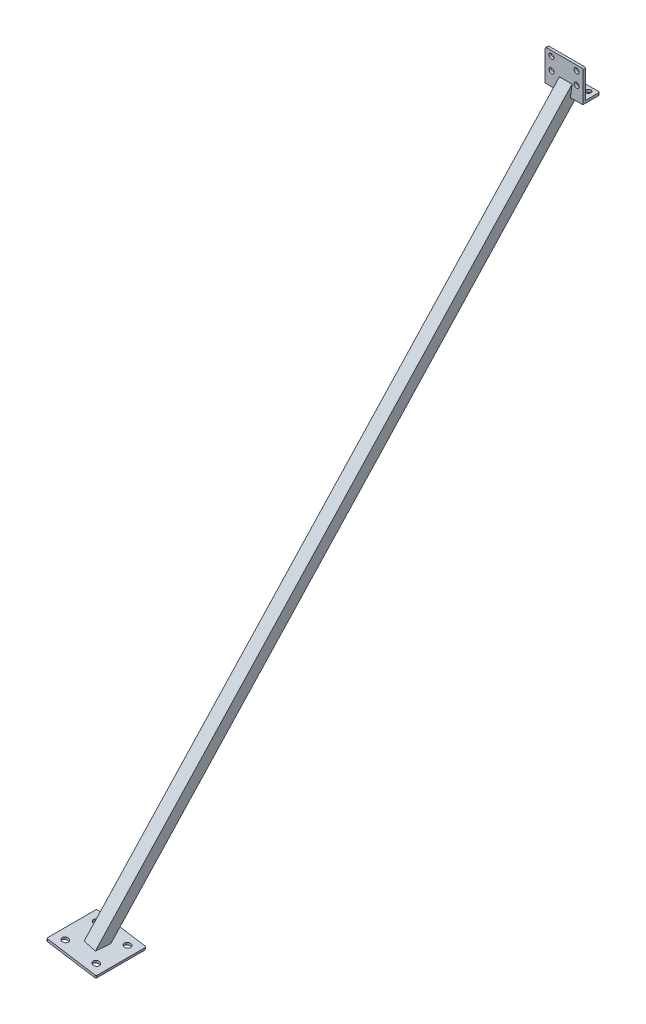
SolidWorks part; units mm, degrees
ref_plane "Front Plane" through (0, 0, 0) normal (0, 0, 1) x (1, 0, 0)
ref_plane "Top Plane" through (0, 0, 0) normal (0, 1, 0) x (1, 0, 0)
ref_plane "Right Plane" through (0, 0, 0) normal (1, 0, 0) x (0, 0, -1)
sketch "Sketch1" plane through (0, 0, 0) normal (1, 0, 0) x (0, 0, -1)
  line L0 (0, 0) -> (0, 50)
  line L1 (0, 50) -> (4, 50)
  line L2 (4, 50) -> (4, 4)
  line L3 (4, 4) -> (27, 4)
  line L4 (27, 4) -> (27, 0)
  line L5 (27, 0) -> (0, 0)
  dimension "D1" = 4
  dimension "D2" = 4
  dimension "D3" = 50
  dimension "D4" = 27
extrude "Boss-Extrude1" add sketch "Sketch1" along normal blind 60
ref_plane "Plane1" through (0, 0, 0) normal (0, -0.866, 0.5) x (-1, 0, 0)
sketch "Sketch2" plane through (0, 0, 0) normal (0, -0.866, 0.5) x (-1, 0, 0)
  line L0 (-30, 0) -> (-30, 23.3827)
  line L1 (-60, 0) -> (0, 0) construction
  line L2 (-60, 23.3827) -> (0, 23.3827) construction
ref_plane "Plane2" through (0.7342, 4.0142, -2.3176) normal (-0.1564, -0.8554, 0.4938) x (0, -0.5, -0.866)
sketch "Sketch3" plane through (0.7342, 4.0142, -2.3176) normal (-0.1564, -0.8554, 0.4938) x (0, -0.5, -0.866)
  line L0 (-9, 38.6307) -> (9, 38.6307)
  line L1 (-10, 39.6307) -> (10, 39.6307)
  line L2 (-10, 39.6307) -> (-10, 19.6307)
  line L3 (-10, 19.6307) -> (10, 19.6307)
  line L4 (10, 39.6307) -> (10, 19.6307)
  line L5 (-10, 39.6307) -> (10, 19.6307) construction
  line L6 (-10, 19.6307) -> (10, 39.6307) construction
  line L7 (9, 38.6307) -> (9, 20.6307)
  line L8 (-9, 20.6307) -> (9, 20.6307)
  line L9 (-9, 38.6307) -> (-9, 20.6307)
  point P0 (0, 29.6307)
  dimension "D1" = 20
  dimension "D2" = 20
  dimension "D3" = 1
extrude "Boss-Extrude2" add sketch "Sketch3" along normal blind 2000 and the other way blind 20
sketch "Sketch4" plane through (0, 0, 0) normal (-1, 0, 0) x (0, 0, 1)
  line L0 (-4, 4) -> (-4, 34.4259)
  line L1 (-4, 4) -> (-4, 50) construction
  line L2 (-4, 34.4259) -> (-31.384, 4)
  line L3 (-27, 4) -> (-4, 4) construction
  line L4 (-31.384, 4) -> (-4, 4)
extrude "Cut-Extrude1" cut sketch "Sketch4" against normal blind 60
ref_plane "Plane3" through (-155.5473, -982.0868, 0) normal (0.1564, 0.9877, 0) x (0.9877, -0.1564, 0)
sketch "Sketch6" plane through (-155.5473, -982.0868, 0) normal (0.1564, 0.9877, 0) x (0.9877, -0.1564, 0)
  line L0 (-2.5847, -997.1308) -> (-22.5192, -995.5664) construction
  line L2 (19.2115, 0) -> (-22.5192, -995.5664) construction
  line L4 (45.477, -526.4414) -> (-34.523, -526.4414)
  line L5 (45.477, -526.4414) -> (45.477, -606.4414)
  line L6 (45.477, -606.4414) -> (-34.523, -606.4414)
  line L7 (-34.523, -526.4414) -> (-34.523, -606.4414)
  line L8 (45.477, -526.4414) -> (-34.523, -606.4414) construction
  line L9 (45.477, -606.4414) -> (-34.523, -526.4414) construction
  point P0 (5.477, -566.4414)
  point P6 (5.477, -566.4414)
  dimension "D1" = 430
  dimension "D2" = 10
  dimension "D3" = 80
  dimension "D4" = 80
extrude "Boss-Extrude3" add sketch "Sketch6" along normal blind 4
sketch "Sketch7" plane through (-155.5473, -982.0868, 0) normal (-0.1564, -0.9877, 0) x (0.9877, -0.1564, 0)
  line L1 (-84.9465, 1031.7358) -> (70.9442, 1031.7358)
  line L2 (-84.9465, 1031.7358) -> (-84.9465, 540.4439)
  line L3 (-84.9465, 540.4439) -> (70.9442, 540.4439)
  line L4 (70.9442, 1031.7358) -> (70.9442, 540.4439)
extrude "Cut-Extrude2" cut sketch "Sketch7" along normal blind 1000
sketch "Sketch8" plane through (0, 0, 0) normal (0, 0, 1) x (1, 0, 0)
  circle A0 centre (10, 22) radius 4 construction
  circle A1 centre (50, 22) radius 4 construction
  circle A2 centre (50, 42) radius 4 construction
  circle A3 centre (10, 42) radius 4 construction
  circle A4 centre (10, 22) radius 4
  circle A5 centre (50, 22) radius 4
  circle A6 centre (50, 42) radius 4
  circle A7 centre (10, 42) radius 4
extrude "Cut-Extrude3" cut sketch "Sketch8" against normal up to next
sketch "Sketch9" plane through (0, 0, 0) normal (0, -1, 0) x (1, 0, 0)
  circle A0 centre (50, -19) radius 4 construction
  circle A1 centre (10, -19) radius 4 construction
  circle A2 centre (50, -19) radius 4
  circle A3 centre (10, -19) radius 4
extrude "Cut-Extrude4" cut sketch "Sketch9" against normal up to next
sketch "Sketch10" plane through (-155.5473, -982.0868, 0) normal (-0.1564, -0.9877, 0) x (0.9877, -0.1564, 0)
  line L0 (-34.523, 606.4414) -> (45.477, 606.4414) construction
  line L1 (-34.523, 526.4414) -> (-34.523, 606.4414) construction
  circle A0 centre (-19.523, 591.4414) radius 5
  circle A1 centre (30.477, 591.4414) radius 5
  circle A2 centre (30.477, 541.4414) radius 5
  circle A3 centre (-19.523, 541.4414) radius 5
  dimension "D1" = 10
  dimension "D2" = 15
  dimension "D3" = 15
  dimension "D4" = 2
  dimension "D5" = 2
extrude "Cut-Extrude5" cut sketch "Sketch10" against normal up to next
fillet "Fillet1" radius 2 4 edges at (-189.3323, -974.7108, 606.4414) (-189.3323, -974.7108, 526.4414) (-110.3173, -987.2256, 526.4414) (-110.3173, -987.2256, 606.4414)
fillet "Fillet2" radius 2 4 edges at (60, 2, -27) (0, 2, -27) (60, 50, -2) (0, 50, -2)
